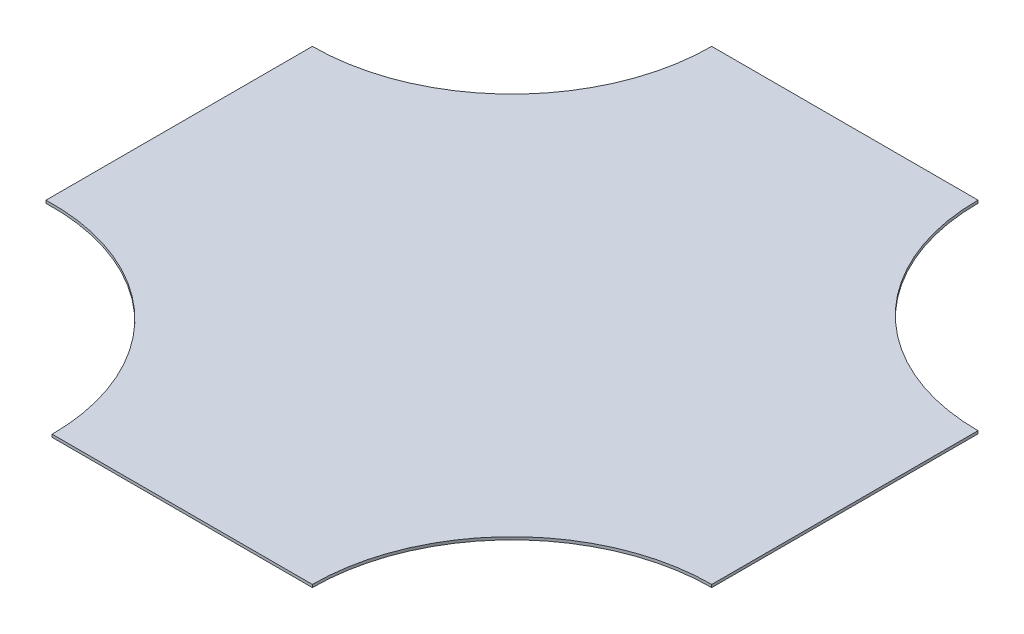
SolidWorks part; units mm, degrees
ref_plane "Front Plane" through (0, 0, 0) normal (0, 0, 1) x (1, 0, 0)
ref_plane "Top Plane" through (0, 0, 0) normal (0, 1, 0) x (1, 0, 0)
ref_plane "Right Plane" through (0, 0, 0) normal (1, 0, 0) x (0, 0, -1)
sketch "Sketch1" plane through (0, 0, 0) normal (0, 1, 0) x (1, 0, 0)
  line L5 (-145.4402, -381) -> (152.4, -381)
  line L6 (-381, -152.506) -> (-381, 152.4)
  line L7 (-152.4, 381) -> (152.4, 381)
  line L8 (381, -152.4) -> (381, 152.4)
  line L9 (-215.913, -215.913) -> (219.3554, 219.3554) construction
  line L10 (-219.3554, 219.3554) -> (219.3554, -219.3554) construction
  arc A4 (-381, 152.4) -> (-152.4, 381) centre (-381, 381) ccw
  arc A5 (-145.4402, -381) -> (-381, -152.506) centre (-374.0402, -381) ccw
  arc A6 (381, -152.4) -> (152.4, -381) centre (381, -381) ccw
  arc A7 (152.4, 381) -> (381, 152.4) centre (381, 381) ccw
  point P0 (0, 0)
  point P1 (0, 0)
  dimension "D3" = 457.2
  dimension "D4" = 457.2
  dimension "D5" = 457.2
  dimension "D6" = 457.2
  dimension "D1" = 762
extrude "Boss-Extrude1" add sketch "Sketch1" along normal blind 3.175
